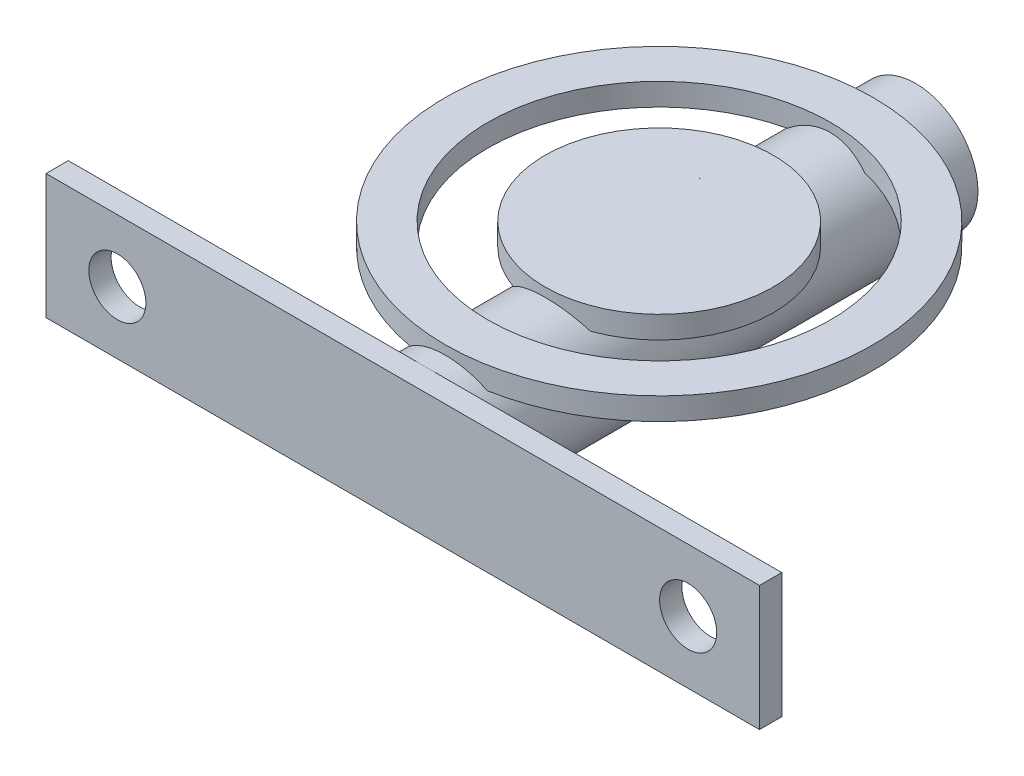
SolidWorks part; units mm, degrees
ref_plane "前视基准面" through (0, 0, 0) normal (0, 0, 1) x (1, 0, 0)
ref_plane "上视基准面" through (0, 0, 0) normal (0, 1, 0) x (1, 0, 0)
ref_plane "右视基准面" through (0, 0, 0) normal (1, 0, 0) x (0, 0, -1)
sketch "草图1" plane through (0, 0, 0) normal (0, 0, 1) x (1, 0, 0)
  circle A0 centre (0, 0) radius 3.5
extrude "凸台-拉伸1" add sketch "草图1" along normal blind 27.5
sketch "草图2" plane through (0, 0, 0) normal (0, 0, -1) x (-1, 0, 0)
  circle A0 centre (0, 0) radius 2.25
extrude "切除-拉伸1" cut sketch "草图2" against normal blind 8.2
sketch "草图3" plane through (0, 0, 27.5) normal (0, 0, 1) x (1, 0, 0)
  line L1 (-20, 3.5) -> (20, 3.5)
  line L2 (-20, 3.5) -> (-20, -3.5)
  line L3 (-20, -3.5) -> (20, -3.5)
  line L4 (20, 3.5) -> (20, -3.5)
  circle A0 centre (-16, 0) radius 1.6
  circle A1 centre (16, 0) radius 1.6
  point P6 (0, 0)
  point P7 (0, 0)
  point P10 (0, 0)
  point P11 (0, 0)
  point P12 (0, 0)
  point P13 (0, 0)
  point P14 (0, 0)
  point P15 (0, 0)
extrude "凸台-拉伸2" add sketch "草图3" along normal blind 1.25 contours L1 L4 L3 L2
extrude "切除-拉伸3" cut sketch "草图3<4>" along normal blind 1.5 contours A0 | A1
sketch "草图3<4>" plane through (0, 0, 27.5) normal (0, 0, 1) x (1, 0, 0) same geometry as "草图3"
sketch "草图6" plane through (0, 3.5, 0) normal (0, 1, 0) x (1, 0, 0)
  line L0 (0, -28.75) -> (0, 0)
  line L1 (-20, -28.75) -> (20, -28.75) construction
  circle A0 centre (0, -14.375) radius 12
  circle A1 centre (0, -14.375) radius 6.4
  circle A2 centre (0, -14.375) radius 9.6
extrude "凸台-拉伸3" add sketch "草图6" along normal blind 0.5 and the other way blind 0.75 contours L0 A1 | L0 A1 | A2 L0 A0 | A2 L0 A0 region at (-11.7317, 3.5, 14.375) region at (0.2683, 3.5, 25.175) region at (-2.7162, 3.5, 14.375) region at (2.7162, 3.5, 14.375)
